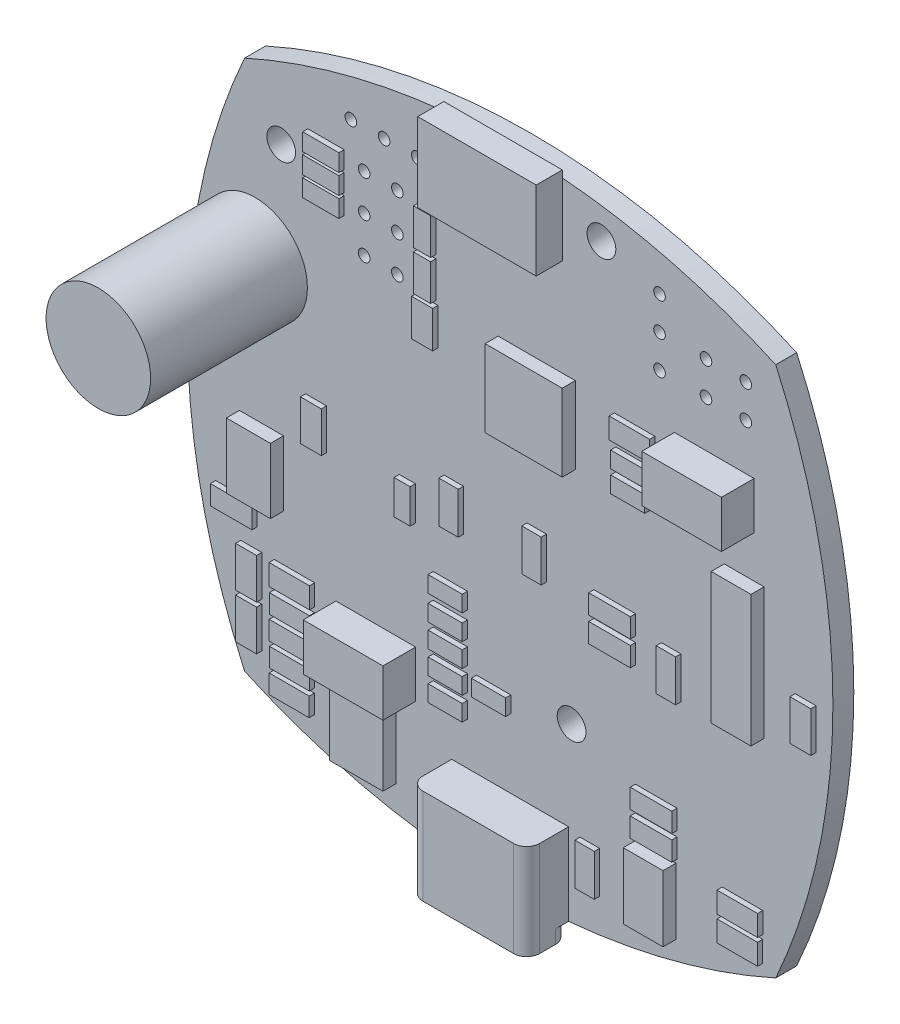
SolidWorks part; units mm, degrees
ref_plane "前视基准面" through (0, 0, 0) normal (0, 0, 1) x (1, 0, 0)
ref_plane "上视基准面" through (0, 0, 0) normal (0, 1, 0) x (1, 0, 0)
ref_plane "右视基准面" through (0, 0, 0) normal (1, 0, 0) x (0, 0, -1)
sketch "Model" plane through (0, 0, 0) normal (0, 0, 1) x (1, 0, 0)
  line L0 (-8.89, -4.699) -> (-11.4046, -4.699)
  line L1 (-11.4046, -4.699) -> (-11.4046, 0.381)
  line L2 (-11.4046, 0.381) -> (-8.89, 0.381)
  line L3 (-8.89, 0.381) -> (-8.89, -4.699)
  line L4 (10.788, 6.8768) -> (10.788, 6.0767)
  line L5 (9.6783, 7.1866) -> (10.4782, 7.1866)
  line L6 (9.6783, 5.767) -> (10.4782, 5.767)
  line L7 (9.1024, 7.1924) -> (8.3024, 7.1924)
  line L8 (7.9925, 6.8826) -> (7.9925, 6.0826)
  line L9 (9.1024, 5.7728) -> (8.3024, 5.7728)
  line L10 (1.432, 0.38) -> (2.632, 0.38)
  line L11 (1.232, -1.67) -> (1.232, -2.67)
  line L12 (2.832, -1.67) -> (2.832, -2.67)
  line L13 (1.232, -0.8699) -> (1.232, 0.13)
  line L14 (2.832, -0.8699) -> (2.832, 0.13)
  line L15 (1.432, -2.92) -> (2.632, -2.92)
  line L16 (1.232, -2.72) -> (1.232, -2.67)
  line L17 (2.832, -2.72) -> (2.832, -2.67)
  line L18 (1.232, 0.18) -> (1.232, 0.13)
  line L19 (2.832, 0.18) -> (2.832, 0.13)
  line L20 (10.788, 8.5278) -> (10.788, 7.7277)
  line L21 (9.6783, 8.8376) -> (10.4782, 8.8376)
  line L22 (9.6783, 7.418) -> (10.4782, 7.418)
  line L23 (9.1024, 8.8434) -> (8.3024, 8.8434)
  line L24 (7.9925, 8.5336) -> (7.9925, 7.7336)
  line L25 (9.1024, 7.4238) -> (8.3024, 7.4238)
  line L26 (-6.7498, 11.296) -> (-5.9497, 11.296)
  line L27 (-7.0596, 10.1863) -> (-7.0596, 10.9862)
  line L28 (-5.64, 10.1863) -> (-5.64, 10.9862)
  line L29 (-7.0654, 9.6104) -> (-7.0654, 8.8104)
  line L30 (-6.7556, 8.5005) -> (-5.9556, 8.5005)
  line L31 (-5.6458, 9.6104) -> (-5.6458, 8.8104)
  line L32 (5.496, -18.416) -> (6.696, -18.416)
  line L33 (5.296, -20.466) -> (5.296, -21.466)
  line L34 (6.896, -20.466) -> (6.896, -21.466)
  line L35 (5.296, -19.6659) -> (5.296, -18.666)
  line L36 (6.896, -19.6659) -> (6.896, -18.666)
  line L37 (5.496, -21.716) -> (6.696, -21.716)
  line L38 (5.296, -21.516) -> (5.296, -21.466)
  line L39 (6.896, -21.516) -> (6.896, -21.466)
  line L40 (5.296, -18.616) -> (5.296, -18.666)
  line L41 (6.896, -18.616) -> (6.896, -18.666)
  line L42 (9.651, -3.591) -> (9.651, -4.791)
  line L43 (7.601, -3.391) -> (6.601, -3.391)
  line L44 (7.601, -4.991) -> (6.601, -4.991)
  line L45 (8.4011, -3.391) -> (9.401, -3.391)
  line L46 (8.4011, -4.991) -> (9.401, -4.991)
  line L47 (6.351, -3.591) -> (6.351, -4.791)
  line L48 (6.551, -3.391) -> (6.601, -3.391)
  line L49 (6.551, -4.991) -> (6.601, -4.991)
  line L50 (9.451, -3.391) -> (9.401, -3.391)
  line L51 (9.451, -4.991) -> (9.401, -4.991)
  line L52 (9.651, -1.686) -> (9.651, -2.886)
  line L53 (7.601, -1.486) -> (6.601, -1.486)
  line L54 (7.601, -3.086) -> (6.601, -3.086)
  line L55 (8.4011, -1.486) -> (9.401, -1.486)
  line L56 (8.4011, -3.086) -> (9.401, -3.086)
  line L57 (6.351, -1.686) -> (6.351, -2.886)
  line L58 (6.551, -1.486) -> (6.601, -1.486)
  line L59 (6.551, -3.086) -> (6.601, -3.086)
  line L60 (9.451, -1.486) -> (9.401, -1.486)
  line L61 (9.451, -3.086) -> (9.401, -3.086)
  line L62 (9.526, -14.189) -> (9.526, -12.989)
  line L63 (11.576, -14.389) -> (12.576, -14.389)
  line L64 (11.576, -12.789) -> (12.576, -12.789)
  line L65 (10.7759, -14.389) -> (9.776, -14.389)
  line L66 (10.7759, -12.789) -> (9.776, -12.789)
  line L67 (12.826, -14.189) -> (12.826, -12.989)
  line L68 (12.626, -14.389) -> (12.576, -14.389)
  line L69 (12.626, -12.789) -> (12.576, -12.789)
  line L70 (9.726, -14.389) -> (9.776, -14.389)
  line L71 (9.726, -12.789) -> (9.776, -12.789)
  line L72 (-3.718, -2.92) -> (-4.918, -2.92)
  line L73 (-3.518, -0.87) -> (-3.518, 0.13)
  line L74 (-5.118, -0.87) -> (-5.118, 0.13)
  line L75 (-3.518, -1.6701) -> (-3.518, -2.67)
  line L76 (-5.118, -1.6701) -> (-5.118, -2.67)
  line L77 (-3.718, 0.38) -> (-4.918, 0.38)
  line L78 (-3.518, 0.18) -> (-3.518, 0.13)
  line L79 (-5.118, 0.18) -> (-5.118, 0.13)
  line L80 (-3.518, -2.72) -> (-3.518, -2.67)
  line L81 (-5.118, -2.72) -> (-5.118, -2.67)
  line L82 (12.919, -5.714) -> (11.719, -5.714)
  line L83 (13.119, -3.664) -> (13.119, -2.664)
  line L84 (11.519, -3.664) -> (11.519, -2.664)
  line L85 (13.119, -4.4641) -> (13.119, -5.464)
  line L86 (11.519, -4.4641) -> (11.519, -5.464)
  line L87 (12.919, -2.414) -> (11.719, -2.414)
  line L88 (13.119, -2.614) -> (13.119, -2.664)
  line L89 (11.519, -2.614) -> (11.519, -2.664)
  line L90 (13.119, -5.514) -> (13.119, -5.464)
  line L91 (11.519, -5.514) -> (11.519, -5.464)
  line L92 (12.826, -14.894) -> (12.826, -16.094)
  line L93 (10.776, -14.694) -> (9.776, -14.694)
  line L94 (10.776, -16.294) -> (9.776, -16.294)
  line L95 (11.5761, -14.694) -> (12.576, -14.694)
  line L96 (11.5761, -16.294) -> (12.576, -16.294)
  line L97 (9.526, -14.894) -> (9.526, -16.094)
  line L98 (9.726, -14.694) -> (9.776, -14.694)
  line L99 (9.726, -16.294) -> (9.776, -16.294)
  line L100 (12.626, -14.694) -> (12.576, -14.694)
  line L101 (12.626, -16.294) -> (12.576, -16.294)
  line L102 (-22.3748, 8.2296) -> (-22.3748, 9.5758)
  line L103 (-21.7398, 8.9154) -> (-22.9844, 8.9154)
  line L104 (-12.354, -2.793) -> (-13.554, -2.793)
  line L105 (-12.154, -0.743) -> (-12.154, 0.257)
  line L106 (-13.754, -0.743) -> (-13.754, 0.257)
  line L107 (-12.154, -1.5431) -> (-12.154, -2.543)
  line L108 (-13.754, -1.5431) -> (-13.754, -2.543)
  line L109 (-12.354, 0.507) -> (-13.554, 0.507)
  line L110 (-12.154, 0.307) -> (-12.154, 0.257)
  line L111 (-13.754, 0.307) -> (-13.754, 0.257)
  line L112 (-12.154, -2.593) -> (-12.154, -2.543)
  line L113 (-13.754, -2.593) -> (-13.754, -2.543)
  line L114 (-22.605, -10.125) -> (-22.605, -8.925)
  line L115 (-20.555, -10.325) -> (-19.555, -10.325)
  line L116 (-20.555, -8.725) -> (-19.555, -8.725)
  line L117 (-21.3551, -10.325) -> (-22.355, -10.325)
  line L118 (-21.3551, -8.725) -> (-22.355, -8.725)
  line L119 (-19.305, -10.125) -> (-19.305, -8.925)
  line L120 (-19.505, -10.325) -> (-19.555, -10.325)
  line L121 (-19.505, -8.725) -> (-19.555, -8.725)
  line L122 (-22.405, -10.325) -> (-22.355, -10.325)
  line L123 (-22.405, -8.725) -> (-22.355, -8.725)
  line L124 (-3.182, -6.7122) -> (-3.182, -7.5123)
  line L125 (-4.2917, -6.4024) -> (-3.4918, -6.4024)
  line L126 (-4.2917, -7.822) -> (-3.4918, -7.822)
  line L127 (-4.8676, -6.3966) -> (-5.6676, -6.3966)
  line L128 (-5.9775, -6.7064) -> (-5.9775, -7.5064)
  line L129 (-4.8676, -7.8162) -> (-5.6676, -7.8162)
  line L130 (-3.182, -8.6172) -> (-3.182, -9.4173)
  line L131 (-4.2917, -8.3074) -> (-3.4918, -8.3074)
  line L132 (-4.2917, -9.727) -> (-3.4918, -9.727)
  line L133 (-4.8676, -8.3016) -> (-5.6676, -8.3016)
  line L134 (-5.9775, -8.6114) -> (-5.9775, -9.4114)
  line L135 (-4.8676, -9.7212) -> (-5.6676, -9.7212)
  line L136 (-3.182, -10.3952) -> (-3.182, -11.1953)
  line L137 (-4.2917, -10.0854) -> (-3.4918, -10.0854)
  line L138 (-4.2917, -11.505) -> (-3.4918, -11.505)
  line L139 (-4.8676, -10.0796) -> (-5.6676, -10.0796)
  line L140 (-5.9775, -10.3894) -> (-5.9775, -11.1894)
  line L141 (-4.8676, -11.4992) -> (-5.6676, -11.4992)
  line L142 (-3.182, -12.1732) -> (-3.182, -12.9733)
  line L143 (-4.2917, -11.8634) -> (-3.4918, -11.8634)
  line L144 (-4.2917, -13.283) -> (-3.4918, -13.283)
  line L145 (-4.8676, -11.8576) -> (-5.6676, -11.8576)
  line L146 (-5.9775, -12.1674) -> (-5.9775, -12.9674)
  line L147 (-4.8676, -13.2772) -> (-5.6676, -13.2772)
  line L148 (-6.3688, -20.835) -> (-5.5687, -20.835)
  line L149 (-6.6786, -21.9447) -> (-6.6786, -21.1448)
  line L150 (-5.259, -21.9447) -> (-5.259, -21.1448)
  line L151 (-6.6844, -22.5206) -> (-6.6844, -23.3206)
  line L152 (-6.3746, -23.6305) -> (-5.5746, -23.6305)
  line L153 (-5.2648, -22.5206) -> (-5.2648, -23.3206)
  line L154 (-7.4742, -4.057) -> (-8.2743, -4.057)
  line L155 (-7.1644, -2.9473) -> (-7.1644, -3.7472)
  line L156 (-8.584, -2.9473) -> (-8.584, -3.7472)
  line L157 (-7.1586, -2.3714) -> (-7.1586, -1.5714)
  line L158 (-7.4684, -1.2615) -> (-8.2684, -1.2615)
  line L159 (-8.5782, -2.3714) -> (-8.5782, -1.5714)
  line L160 (-3.182, -13.9512) -> (-3.182, -14.7513)
  line L161 (-4.2917, -13.6414) -> (-3.4918, -13.6414)
  line L162 (-4.2917, -15.061) -> (-3.4918, -15.061)
  line L163 (-4.8676, -13.6356) -> (-5.6676, -13.6356)
  line L164 (-5.9775, -13.9454) -> (-5.9775, -14.7454)
  line L165 (-4.8676, -15.0552) -> (-5.6676, -15.0552)
  line L166 (-2.66, -12.7188) -> (-2.66, -11.9187)
  line L167 (-1.5503, -13.0286) -> (-2.3502, -13.0286)
  line L168 (-1.5503, -11.609) -> (-2.3502, -11.609)
  line L169 (-0.9744, -13.0344) -> (-0.1744, -13.0344)
  line L170 (0.1355, -12.7246) -> (0.1355, -11.9246)
  line L171 (-0.9744, -11.6148) -> (-0.1744, -11.6148)
  line L172 (-22.86, 0.635) -> (-22.4536, -0.381)
  line L173 (-22.4536, -0.381) -> (-23.2664, -0.381)
  line L174 (-23.2664, -0.381) -> (-22.86, 0.635)
  line L175 (-21.86, 1.627) -> (-21.86, -1.373)
  line L176 (-23.86, 1.627) -> (-23.86, -1.373)
  line L177 (-22.352, 0.635) -> (-23.368, 0.635)
  line L178 (-22.86, 0.889) -> (-22.86, -0.635)
  line L179 (-7.366, 13.081) -> (-7.366, 10.5664)
  line L180 (-7.366, 10.5664) -> (-12.446, 10.5664)
  line L181 (-12.446, 10.5664) -> (-12.446, 13.081)
  line L182 (-12.446, 13.081) -> (-7.366, 13.081)
  line L183 (-7.366, 15.875) -> (-7.366, 13.3604)
  line L184 (-7.366, 13.3604) -> (-12.446, 13.3604)
  line L185 (-12.446, 13.3604) -> (-12.446, 15.875)
  line L186 (-12.446, 15.875) -> (-7.366, 15.875)
  line L187 (-7.366, 18.669) -> (-7.366, 16.1544)
  line L188 (-7.366, 16.1544) -> (-12.446, 16.1544)
  line L189 (-12.446, 16.1544) -> (-12.446, 18.669)
  line L190 (-12.446, 18.669) -> (-7.366, 18.669)
  line L191 (16.764, 19.304) -> (19.2786, 19.304)
  line L192 (19.2786, 19.304) -> (19.2786, 14.224)
  line L193 (19.2786, 14.224) -> (16.764, 14.224)
  line L194 (16.764, 14.224) -> (16.764, 19.304)
  line L195 (13.716, 19.304) -> (16.2306, 19.304)
  line L196 (16.2306, 19.304) -> (16.2306, 14.224)
  line L197 (16.2306, 14.224) -> (13.716, 14.224)
  line L198 (13.716, 14.224) -> (13.716, 19.304)
  line L199 (12.7, 19.939) -> (12.7, 21.844)
  line L200 (12.7, 21.844) -> (10.16, 21.844)
  line L201 (10.16, 21.844) -> (10.16, 14.224)
  line L202 (10.16, 14.224) -> (12.7, 14.224)
  line L203 (12.7, 14.224) -> (12.7, 19.939)
  line L204 (10.922, 4.445) -> (10.922, 1.905)
  line L205 (10.922, 1.905) -> (13.462, 1.905)
  line L206 (13.462, 4.445) -> (13.462, 0.619)
  line L207 (5.842, 0.635) -> (5.842, 3.175)
  line L208 (7.112, 4.445) -> (13.462, 4.445)
  line L209 (12.1873, -0.635) -> (7.112, -0.635)
  line L210 (-14.4212, -6.4426) -> (-14.4212, -4.9288)
  line L211 (-14.4212, -4.9288) -> (-7.1688, -4.9288)
  line L212 (-7.1688, -4.9288) -> (-7.1688, -6.4426)
  line L213 (-14.4212, -10.0674) -> (-14.4212, -11.5812)
  line L214 (-14.4212, -11.5812) -> (-7.1688, -11.5812)
  line L215 (-7.1688, -11.5812) -> (-7.1688, -10.0674)
  line L216 (-16.88, -15.208) -> (-18.03, -15.208)
  line L217 (-18.03, -15.208) -> (-18.03, -13.758)
  line L218 (-18.03, -13.758) -> (-16.83, -13.758)
  line L219 (-16.21, -13.748) -> (-14.97, -13.748)
  line L220 (-14.97, -13.748) -> (-14.97, -15.198)
  line L221 (-14.97, -15.198) -> (-16.21, -15.198)
  line L222 (-18.03, -15.208) -> (-18.06, -15.208)
  line L223 (-18.06, -15.208) -> (-18.26, -15.008)
  line L224 (-18.26, -15.008) -> (-18.26, -13.988)
  line L225 (-18.26, -13.988) -> (-18.23, -13.958)
  line L226 (-18.23, -13.958) -> (-18.03, -13.758)
  line L227 (-16.14, -15.526) -> (-14.99, -15.526)
  line L228 (-14.99, -15.526) -> (-14.99, -16.976)
  line L229 (-14.99, -16.976) -> (-16.19, -16.976)
  line L230 (-16.81, -16.986) -> (-18.05, -16.986)
  line L231 (-18.05, -16.986) -> (-18.05, -15.536)
  line L232 (-18.05, -15.536) -> (-16.81, -15.536)
  line L233 (-14.99, -15.526) -> (-14.96, -15.526)
  line L234 (-14.96, -15.526) -> (-14.76, -15.726)
  line L235 (-14.76, -15.726) -> (-14.76, -16.746)
  line L236 (-14.76, -16.746) -> (-14.79, -16.776)
  line L237 (-14.79, -16.776) -> (-14.99, -16.976)
  line L238 (-16.88, -18.764) -> (-18.03, -18.764)
  line L239 (-18.03, -18.764) -> (-18.03, -17.314)
  line L240 (-18.03, -17.314) -> (-16.83, -17.314)
  line L241 (-16.21, -17.304) -> (-14.97, -17.304)
  line L242 (-14.97, -17.304) -> (-14.97, -18.754)
  line L243 (-14.97, -18.754) -> (-16.21, -18.754)
  line L244 (-18.03, -18.764) -> (-18.06, -18.764)
  line L245 (-18.06, -18.764) -> (-18.26, -18.564)
  line L246 (-18.26, -18.564) -> (-18.26, -17.544)
  line L247 (-18.26, -17.544) -> (-18.23, -17.514)
  line L248 (-18.23, -17.514) -> (-18.03, -17.314)
  line L249 (-16.14, -19.082) -> (-14.99, -19.082)
  line L250 (-14.99, -19.082) -> (-14.99, -20.532)
  line L251 (-14.99, -20.532) -> (-16.19, -20.532)
  line L252 (-16.81, -20.542) -> (-18.05, -20.542)
  line L253 (-18.05, -20.542) -> (-18.05, -19.092)
  line L254 (-18.05, -19.092) -> (-16.81, -19.092)
  line L255 (-14.99, -19.082) -> (-14.96, -19.082)
  line L256 (-14.96, -19.082) -> (-14.76, -19.282)
  line L257 (-14.76, -19.282) -> (-14.76, -20.302)
  line L258 (-14.76, -20.302) -> (-14.79, -20.332)
  line L259 (-14.79, -20.332) -> (-14.99, -20.532)
  line L260 (-13.8788, 5.5902) -> (-15.3312, 5.5902)
  line L261 (-15.3312, 5.5902) -> (-15.3312, 4.5586)
  line L262 (-13.8788, 2.5378) -> (-15.3312, 2.5378)
  line L263 (-15.3312, 2.5378) -> (-15.3312, 3.5694)
  line L264 (-13.8788, 4.5194) -> (-13.8788, 3.6086)
  line L265 (-10.3228, 5.5902) -> (-11.7752, 5.5902)
  line L266 (-11.7752, 5.5902) -> (-11.7752, 4.5586)
  line L267 (-10.3228, 2.5378) -> (-11.7752, 2.5378)
  line L268 (-11.7752, 2.5378) -> (-11.7752, 3.5694)
  line L269 (-10.3228, 4.5194) -> (-10.3228, 3.6086)
  line L270 (-10.3228, 9.1462) -> (-11.7752, 9.1462)
  line L271 (-11.7752, 9.1462) -> (-11.7752, 8.1146)
  line L272 (-10.3228, 6.0938) -> (-11.7752, 6.0938)
  line L273 (-11.7752, 6.0938) -> (-11.7752, 7.1254)
  line L274 (-10.3228, 8.0754) -> (-10.3228, 7.1646)
  line L275 (11.075, 9.36) -> (11.075, 10.96)
  line L276 (9.2243, 10.9549) -> (7.9744, 10.9549)
  line L277 (9.2243, 9.3549) -> (7.9744, 9.3549)
  line L278 (9.8249, 10.96) -> (11.075, 10.96)
  line L279 (9.8249, 9.36) -> (11.075, 9.36)
  line L280 (7.9744, 9.3549) -> (7.9744, 10.9549)
  line L281 (6.124, -7.7051) -> (6.124, -8.0429)
  line L282 (7.9741, -6.374) -> (7.0554, -6.374)
  line L283 (9.7742, -8.9052) -> (9.7742, -9.3741)
  line L284 (9.7742, -6.3741) -> (9.7742, -6.8428)
  line L285 (9.7742, -8.9052) -> (9.7742, -9.3741)
  line L286 (9.7742, -6.3741) -> (9.7742, -6.8428)
  line L287 (9.7742, -9.3741) -> (7.0554, -9.3741)
  line L288 (9.7742, -8.9052) -> (9.7742, -9.3741)
  line L289 (9.7742, -6.3741) -> (9.7742, -6.8428)
  line L290 (7.9741, -6.3741) -> (9.7742, -6.3741)
  line L291 (7.9741, -9.3741) -> (9.7742, -9.3741)
  line L292 (23.406, -0.736) -> (21.806, -0.736)
  line L293 (21.8111, -2.5867) -> (21.8111, -3.8366)
  line L294 (23.4111, -2.5867) -> (23.4111, -3.8366)
  line L295 (21.806, -1.9861) -> (21.806, -0.736)
  line L296 (23.406, -1.9861) -> (23.406, -0.736)
  line L297 (23.4111, -3.8366) -> (21.8111, -3.8366)
  line L298 (12.093, -7.7051) -> (12.093, -8.0429)
  line L299 (13.9431, -6.374) -> (13.0244, -6.374)
  line L300 (15.7432, -8.9052) -> (15.7432, -9.3741)
  line L301 (15.7432, -6.3741) -> (15.7432, -6.8428)
  line L302 (15.7432, -8.9052) -> (15.7432, -9.3741)
  line L303 (15.7432, -6.3741) -> (15.7432, -6.8428)
  line L304 (15.7432, -9.3741) -> (13.0244, -9.3741)
  line L305 (15.7432, -8.9052) -> (15.7432, -9.3741)
  line L306 (15.7432, -6.3741) -> (15.7432, -6.8428)
  line L307 (13.9431, -6.3741) -> (15.7432, -6.3741)
  line L308 (13.9431, -9.3741) -> (15.7432, -9.3741)
  line L309 (16.23, -16.345) -> (16.23, -17.945)
  line L310 (18.0807, -17.9399) -> (19.3306, -17.9399)
  line L311 (18.0807, -16.3399) -> (19.3306, -16.3399)
  line L312 (17.4801, -17.945) -> (16.23, -17.945)
  line L313 (17.4801, -16.345) -> (16.23, -16.345)
  line L314 (19.3306, -16.3399) -> (19.3306, -17.9399)
  line L315 (19.33, -19.85) -> (19.33, -18.25)
  line L316 (17.4793, -18.2551) -> (16.2294, -18.2551)
  line L317 (17.4793, -19.8551) -> (16.2294, -19.8551)
  line L318 (18.0799, -18.25) -> (19.33, -18.25)
  line L319 (18.0799, -19.85) -> (19.33, -19.85)
  line L320 (16.2294, -19.8551) -> (16.2294, -18.2551)
  line L321 (-18.06, -11.773) -> (-18.06, -13.373)
  line L322 (-16.2093, -13.3679) -> (-14.9594, -13.3679)
  line L323 (-16.2093, -11.7679) -> (-14.9594, -11.7679)
  line L324 (-16.8099, -13.373) -> (-18.06, -13.373)
  line L325 (-16.8099, -11.773) -> (-18.06, -11.773)
  line L326 (-14.9594, -11.7679) -> (-14.9594, -13.3679)
  line L327 (-20.612, -18.314) -> (-19.012, -18.314)
  line L328 (-19.0171, -16.4633) -> (-19.0171, -15.2134)
  line L329 (-20.6171, -16.4633) -> (-20.6171, -15.2134)
  line L330 (-19.012, -17.0639) -> (-19.012, -18.314)
  line L331 (-20.612, -17.0639) -> (-20.612, -18.314)
  line L332 (-20.6171, -15.2134) -> (-19.0171, -15.2134)
  line L333 (-20.612, -14.885) -> (-19.012, -14.885)
  line L334 (-19.0171, -13.0343) -> (-19.0171, -11.7844)
  line L335 (-20.6171, -13.0343) -> (-20.6171, -11.7844)
  line L336 (-19.012, -13.6349) -> (-19.012, -14.885)
  line L337 (-20.612, -13.6349) -> (-20.612, -14.885)
  line L338 (-20.6171, -11.7844) -> (-19.0171, -11.7844)
  line L339 (-14.059, 0.407) -> (-15.659, 0.407)
  line L340 (-15.6539, -1.4437) -> (-15.6539, -2.6936)
  line L341 (-14.0539, -1.4437) -> (-14.0539, -2.6936)
  line L342 (-15.659, -0.8431) -> (-15.659, 0.407)
  line L343 (-14.059, -0.8431) -> (-14.059, 0.407)
  line L344 (-14.0539, -2.6936) -> (-15.6539, -2.6936)
  line L345 (-5.3084, -18.4968) -> (-5.3084, -17.5379)
  line L346 (-5.3084, -17.5379) -> (-6.6296, -17.5379)
  line L347 (-6.6296, -17.5379) -> (-6.6296, -18.4968)
  line L348 (-5.3084, -19.3492) -> (-5.3084, -20.3081)
  line L349 (-5.3084, -20.3081) -> (-6.6296, -20.3081)
  line L350 (-6.6296, -20.3081) -> (-6.6296, -19.3492)
  line L351 (0.28, -15.151) -> (0.28, -13.551)
  line L352 (-1.5707, -13.5561) -> (-2.8206, -13.5561)
  line L353 (-1.5707, -15.1561) -> (-2.8206, -15.1561)
  line L354 (-0.9701, -13.551) -> (0.28, -13.551)
  line L355 (-0.9701, -15.151) -> (0.28, -15.151)
  line L356 (-2.8206, -15.1561) -> (-2.8206, -13.5561)
  line L357 (-13.6708, 13.6904) -> (-12.7119, 13.6904)
  line L358 (-12.7119, 13.6904) -> (-12.7119, 15.0116)
  line L359 (-12.7119, 15.0116) -> (-13.6708, 15.0116)
  line L360 (-14.5232, 13.6904) -> (-15.4821, 13.6904)
  line L361 (-15.4821, 13.6904) -> (-15.4821, 15.0116)
  line L362 (-15.4821, 15.0116) -> (-14.5232, 15.0116)
  line L363 (-14.5232, 16.5356) -> (-15.4821, 16.5356)
  line L364 (-15.4821, 16.5356) -> (-15.4821, 15.2144)
  line L365 (-15.4821, 15.2144) -> (-14.5232, 15.2144)
  line L366 (-13.6708, 16.5356) -> (-12.7119, 16.5356)
  line L367 (-12.7119, 16.5356) -> (-12.7119, 15.2144)
  line L368 (-12.7119, 15.2144) -> (-13.6708, 15.2144)
  line L369 (-14.5232, 18.0596) -> (-15.4821, 18.0596)
  line L370 (-15.4821, 18.0596) -> (-15.4821, 16.7384)
  line L371 (-15.4821, 16.7384) -> (-14.5232, 16.7384)
  line L372 (-13.6708, 18.0596) -> (-12.7119, 18.0596)
  line L373 (-12.7119, 18.0596) -> (-12.7119, 16.7384)
  line L374 (-12.7119, 16.7384) -> (-13.6708, 16.7384)
  line L375 (-5.6894, 13.3802) -> (-5.6894, 14.3391)
  line L376 (-5.6894, 14.3391) -> (-7.0106, 14.3391)
  line L377 (-7.0106, 14.3391) -> (-7.0106, 13.3802)
  line L378 (-5.6894, 12.5278) -> (-5.6894, 11.5689)
  line L379 (-5.6894, 11.5689) -> (-7.0106, 11.5689)
  line L380 (-7.0106, 11.5689) -> (-7.0106, 12.5278)
  line L381 (-5.6894, 16.4282) -> (-5.6894, 17.3871)
  line L382 (-5.6894, 17.3871) -> (-7.0106, 17.3871)
  line L383 (-7.0106, 17.3871) -> (-7.0106, 16.4282)
  line L384 (-5.6894, 15.5758) -> (-5.6894, 14.6169)
  line L385 (-5.6894, 14.6169) -> (-7.0106, 14.6169)
  line L386 (-7.0106, 14.6169) -> (-7.0106, 15.5758)
  line L387 (12.571, 11.96) -> (18.671, 11.96)
  line L388 (12.571, 8.36) -> (18.671, 8.36)
  line L389 (13.081, 11.43) -> (18.161, 11.43)
  line L390 (18.161, 11.43) -> (18.161, 10.8911)
  line L391 (12.571, 11.96) -> (12.571, 10.8911)
  line L392 (12.571, 9.4289) -> (12.571, 8.36)
  line L393 (18.671, 11.96) -> (18.671, 10.8911)
  line L394 (18.671, 9.4289) -> (18.671, 8.36)
  line L395 (18.161, 9.4289) -> (18.161, 8.89)
  line L396 (18.161, 8.89) -> (13.081, 8.89)
  line L397 (13.081, 8.89) -> (13.081, 9.4289)
  line L398 (13.081, 10.8911) -> (13.081, 11.43)
  line L399 (14.351, 10.795) -> (17.018, 10.795)
  line L400 (17.018, 10.795) -> (17.018, 9.525)
  line L401 (17.018, 9.525) -> (14.351, 9.525)
  line L402 (14.351, 9.525) -> (14.351, 10.795)
  line L403 (-7.237, -15.77) -> (-13.337, -15.77)
  line L404 (-7.237, -12.17) -> (-13.337, -12.17)
  line L405 (-7.747, -15.24) -> (-12.827, -15.24)
  line L406 (-12.827, -15.24) -> (-12.827, -14.7011)
  line L407 (-7.237, -15.77) -> (-7.237, -14.7011)
  line L408 (-7.237, -13.2389) -> (-7.237, -12.17)
  line L409 (-13.337, -15.77) -> (-13.337, -14.7011)
  line L410 (-13.337, -13.2389) -> (-13.337, -12.17)
  line L411 (-12.827, -13.2389) -> (-12.827, -12.7)
  line L412 (-12.827, -12.7) -> (-7.747, -12.7)
  line L413 (-7.747, -12.7) -> (-7.747, -13.2389)
  line L414 (-7.747, -14.7011) -> (-7.747, -15.24)
  line L415 (-9.017, -14.605) -> (-11.684, -14.605)
  line L416 (-11.684, -14.605) -> (-11.684, -13.335)
  line L417 (-11.684, -13.335) -> (-9.017, -13.335)
  line L418 (-9.017, -13.335) -> (-9.017, -14.605)
  line L419 (4.982, 11.5987) -> (-0.918, 11.5987)
  line L420 (-0.918, 11.5987) -> (-0.918, 5.6987)
  line L421 (-0.918, 5.6987) -> (4.982, 5.6987)
  line L422 (4.982, 5.6987) -> (4.982, 11.5987)
  line L423 (16.3856, 5.1532) -> (19.4284, 5.1532)
  line L424 (19.4284, 5.1532) -> (19.4284, -4.8992)
  line L425 (19.4284, -4.8992) -> (16.3856, -4.8992)
  line L426 (16.3856, -4.8992) -> (16.3856, 5.1532)
  line L427 (-18.45, -3.225) -> (-17.35, -3.225)
  line L428 (-17.35, -3.225) -> (-17.35, -8.215)
  line L429 (-17.35, -8.215) -> (-20.7212, -8.215)
  line L430 (-20.7212, -8.215) -> (-20.7212, -3.225)
  line L431 (-20.7212, -3.225) -> (-19.63, -3.225)
  line L432 (9.6546, -16.5238) -> (12.6974, -16.5238)
  line L433 (12.6974, -16.5238) -> (12.6974, -21.5762)
  line L434 (12.6974, -21.5762) -> (9.6546, -21.5762)
  line L435 (9.6546, -21.5762) -> (9.6546, -16.5238)
  line L436 (-8.745, -16.8811) -> (-8.745, -21.9812)
  line L437 (-8.745, -21.9809) -> (-12.845, -21.9809)
  line L438 (-12.845, -21.9809) -> (-12.845, -16.8808)
  line L439 (-9.9949, -16.8811) -> (-8.745, -16.8811)
  line L440 (-11.5951, -16.8811) -> (-12.845, -16.8811)
  line L441 (4.32, -25.527) -> (-4.32, -25.527)
  line L442 (-4.32, -20.0028) -> (-4.32, -21.9212)
  line L443 (4.32, -20.0028) -> (4.32, -21.9212)
  line L444 (0.9571, 0.4299) -> (-3.2429, 0.4299)
  line L445 (-3.2429, 0.4299) -> (-3.2429, -2.9701)
  line L446 (-3.2429, -2.9701) -> (0.9571, -2.9701)
  line L447 (0.9571, -2.9701) -> (0.9571, 0.4299)
  line L448 (-16.8, 2.127) -> (-16.8, -1.873)
  line L449 (-21.3, -1.873) -> (-21.3, 2.127)
  line L450 (-4.9489, 20.193) -> (-4.9489, 18.943)
  line L451 (-4.9489, 18.943) -> (-2.9489, 18.943)
  line L452 (-5.0759, 25.07) -> (3.9921, 25.07)
  line L453 (3.9913, 20.2832) -> (3.9913, 19.0335)
  line L454 (3.9913, 19.0335) -> (1.9923, 19.0335)
  line L455 (-5.0759, 23.114) -> (-5.0759, 25.0759)
  line L456 (3.9921, 25.02) -> (3.9921, 23.033)
  line L457 (-11.557, 21.59) -> (-13.462, 21.59)
  line L458 (-13.462, 21.59) -> (-13.462, 19.05)
  line L459 (-13.462, 19.05) -> (-5.842, 19.05)
  line L460 (-5.842, 19.05) -> (-5.842, 21.59)
  line L461 (-5.842, 21.59) -> (-11.557, 21.59)
  line L462 (-4.62, -22.627) -> (-4.62, -23.227)
  line L463 (-4.62, -23.227) -> (-4.62, -22.627)
  line L464 (-4.02, -22.627) -> (-4.02, -23.227)
  line L465 (-4.02, -23.227) -> (-4.02, -22.627)
  line L466 (4.02, -22.627) -> (4.02, -23.227)
  line L467 (4.02, -23.227) -> (4.02, -22.627)
  line L468 (4.62, -22.627) -> (4.62, -23.227)
  line L469 (4.62, -23.227) -> (4.62, -22.627)
  line L470 (4.02, -18.1971) -> (4.02, -19.2971)
  line L471 (4.02, -19.2971) -> (4.02, -18.1971)
  line L472 (4.62, -18.1971) -> (4.62, -19.2971)
  line L473 (4.62, -19.2971) -> (4.62, -18.1971)
  line L474 (-4.62, -18.1971) -> (-4.62, -19.2971)
  line L475 (-4.62, -19.2971) -> (-4.62, -18.1971)
  line L476 (-4.02, -18.1971) -> (-4.02, -19.2971)
  line L477 (-4.02, -19.2971) -> (-4.02, -18.1971)
  line L478 (9.652, 14.605) -> (9.652, 21.1137) construction
  line L479 (22.987, -0.127) -> (22.987, 2.8893) construction
  line L480 (-3.937, 9.017) -> (-3.937, 16.7322) construction
  arc A0 (-20, -20) -> (20, -20) centre (0, 20.32) ccw
  arc A1 (-20, 20) -> (-20, -20) centre (20.32, 0) ccw
  arc A2 (20, -20) -> (19.9956, 19.9978) centre (-20, -0.0056) ccw
  arc A3 (20, 20) -> (-19.9992, 19.9983) centre (0.0021, -20) ccw
  arc A4 (8.3023, 7.1924) -> (7.9925, 6.8826) centre (8.3023, 6.8826) ccw
  arc A5 (7.9925, 6.0826) -> (8.3023, 5.7728) centre (8.3023, 6.0826) ccw
  arc A6 (10.788, 6.8768) -> (10.4782, 7.1866) centre (10.4782, 6.8768) ccw
  arc A7 (10.4782, 5.767) -> (10.788, 6.0768) centre (10.4782, 6.0768) ccw
  arc A8 (1.232, -2.72) -> (1.432, -2.92) centre (1.432, -2.72) ccw
  arc A9 (2.632, -2.92) -> (2.832, -2.72) centre (2.632, -2.72) ccw
  arc A10 (1.432, 0.38) -> (1.232, 0.18) centre (1.432, 0.18) ccw
  arc A11 (2.832, 0.18) -> (2.632, 0.38) centre (2.632, 0.18) ccw
  arc A12 (8.3023, 8.8434) -> (7.9925, 8.5336) centre (8.3023, 8.5336) ccw
  arc A13 (7.9925, 7.7336) -> (8.3023, 7.4238) centre (8.3023, 7.7336) ccw
  arc A14 (10.788, 8.5278) -> (10.4782, 8.8376) centre (10.4782, 8.5278) ccw
  arc A15 (10.4782, 7.418) -> (10.788, 7.7278) centre (10.4782, 7.7278) ccw
  arc A16 (-7.0654, 8.8103) -> (-6.7556, 8.5005) centre (-6.7556, 8.8103) ccw
  arc A17 (-5.9556, 8.5005) -> (-5.6458, 8.8103) centre (-5.9556, 8.8103) ccw
  arc A18 (-6.7498, 11.296) -> (-7.0596, 10.9862) centre (-6.7498, 10.9862) ccw
  arc A19 (-5.64, 10.9862) -> (-5.9498, 11.296) centre (-5.9498, 10.9862) ccw
  arc A20 (5.296, -21.516) -> (5.496, -21.716) centre (5.496, -21.516) ccw
  arc A21 (6.696, -21.716) -> (6.896, -21.516) centre (6.696, -21.516) ccw
  arc A22 (5.496, -18.416) -> (5.296, -18.616) centre (5.496, -18.616) ccw
  arc A23 (6.896, -18.616) -> (6.696, -18.416) centre (6.696, -18.616) ccw
  arc A24 (6.551, -3.391) -> (6.351, -3.591) centre (6.551, -3.591) ccw
  arc A25 (6.351, -4.791) -> (6.551, -4.991) centre (6.551, -4.791) ccw
  arc A26 (9.651, -3.591) -> (9.451, -3.391) centre (9.451, -3.591) ccw
  arc A27 (9.451, -4.991) -> (9.651, -4.791) centre (9.451, -4.791) ccw
  arc A28 (6.551, -1.486) -> (6.351, -1.686) centre (6.551, -1.686) ccw
  arc A29 (6.351, -2.886) -> (6.551, -3.086) centre (6.551, -2.886) ccw
  arc A30 (9.651, -1.686) -> (9.451, -1.486) centre (9.451, -1.686) ccw
  arc A31 (9.451, -3.086) -> (9.651, -2.886) centre (9.451, -2.886) ccw
  arc A32 (12.626, -14.389) -> (12.826, -14.189) centre (12.626, -14.189) ccw
  arc A33 (12.826, -12.989) -> (12.626, -12.789) centre (12.626, -12.989) ccw
  arc A34 (9.526, -14.189) -> (9.726, -14.389) centre (9.726, -14.189) ccw
  arc A35 (9.726, -12.789) -> (9.526, -12.989) centre (9.726, -12.989) ccw
  arc A36 (-3.518, 0.18) -> (-3.718, 0.38) centre (-3.718, 0.18) ccw
  arc A37 (-4.918, 0.38) -> (-5.118, 0.18) centre (-4.918, 0.18) ccw
  arc A38 (-3.718, -2.92) -> (-3.518, -2.72) centre (-3.718, -2.72) ccw
  arc A39 (-5.118, -2.72) -> (-4.918, -2.92) centre (-4.918, -2.72) ccw
  arc A40 (13.119, -2.614) -> (12.919, -2.414) centre (12.919, -2.614) ccw
  arc A41 (11.719, -2.414) -> (11.519, -2.614) centre (11.719, -2.614) ccw
  arc A42 (12.919, -5.714) -> (13.119, -5.514) centre (12.919, -5.514) ccw
  arc A43 (11.519, -5.514) -> (11.719, -5.714) centre (11.719, -5.514) ccw
  arc A44 (9.726, -14.694) -> (9.526, -14.894) centre (9.726, -14.894) ccw
  arc A45 (9.526, -16.094) -> (9.726, -16.294) centre (9.726, -16.094) ccw
  arc A46 (12.826, -14.894) -> (12.626, -14.694) centre (12.626, -14.894) ccw
  arc A47 (12.626, -16.294) -> (12.826, -16.094) centre (12.626, -16.094) ccw
  arc A48 (-19.5199, 11.4937) -> (-19.4843, 11.4935) centre (-19.5199, 7.4937) ccw
  arc A49 (-12.154, 0.307) -> (-12.354, 0.507) centre (-12.354, 0.307) ccw
  arc A50 (-13.554, 0.507) -> (-13.754, 0.307) centre (-13.554, 0.307) ccw
  arc A51 (-12.354, -2.793) -> (-12.154, -2.593) centre (-12.354, -2.593) ccw
  arc A52 (-13.754, -2.593) -> (-13.554, -2.793) centre (-13.554, -2.593) ccw
  arc A53 (-19.505, -10.325) -> (-19.305, -10.125) centre (-19.505, -10.125) ccw
  arc A54 (-19.305, -8.925) -> (-19.505, -8.725) centre (-19.505, -8.925) ccw
  arc A55 (-22.605, -10.125) -> (-22.405, -10.325) centre (-22.405, -10.125) ccw
  arc A56 (-22.405, -8.725) -> (-22.605, -8.925) centre (-22.405, -8.925) ccw
  arc A57 (-5.6677, -6.3966) -> (-5.9775, -6.7064) centre (-5.6677, -6.7064) ccw
  arc A58 (-5.9775, -7.5064) -> (-5.6677, -7.8162) centre (-5.6677, -7.5064) ccw
  arc A59 (-3.182, -6.7122) -> (-3.4918, -6.4024) centre (-3.4918, -6.7122) ccw
  arc A60 (-3.4918, -7.822) -> (-3.182, -7.5122) centre (-3.4918, -7.5122) ccw
  arc A61 (-5.6677, -8.3016) -> (-5.9775, -8.6114) centre (-5.6677, -8.6114) ccw
  arc A62 (-5.9775, -9.4114) -> (-5.6677, -9.7212) centre (-5.6677, -9.4114) ccw
  arc A63 (-3.182, -8.6172) -> (-3.4918, -8.3074) centre (-3.4918, -8.6172) ccw
  arc A64 (-3.4918, -9.727) -> (-3.182, -9.4172) centre (-3.4918, -9.4172) ccw
  arc A65 (-5.6677, -10.0796) -> (-5.9775, -10.3894) centre (-5.6677, -10.3894) ccw
  arc A66 (-5.9775, -11.1894) -> (-5.6677, -11.4992) centre (-5.6677, -11.1894) ccw
  arc A67 (-3.182, -10.3952) -> (-3.4918, -10.0854) centre (-3.4918, -10.3952) ccw
  arc A68 (-3.4918, -11.505) -> (-3.182, -11.1952) centre (-3.4918, -11.1952) ccw
  arc A69 (-5.6677, -11.8576) -> (-5.9775, -12.1674) centre (-5.6677, -12.1674) ccw
  arc A70 (-5.9775, -12.9674) -> (-5.6677, -13.2772) centre (-5.6677, -12.9674) ccw
  arc A71 (-3.182, -12.1732) -> (-3.4918, -11.8634) centre (-3.4918, -12.1732) ccw
  arc A72 (-3.4918, -13.283) -> (-3.182, -12.9732) centre (-3.4918, -12.9732) ccw
  arc A73 (-6.6844, -23.3207) -> (-6.3746, -23.6305) centre (-6.3746, -23.3207) ccw
  arc A74 (-5.5746, -23.6305) -> (-5.2648, -23.3207) centre (-5.5746, -23.3207) ccw
  arc A75 (-6.3688, -20.835) -> (-6.6786, -21.1448) centre (-6.3688, -21.1448) ccw
  arc A76 (-5.259, -21.1448) -> (-5.5688, -20.835) centre (-5.5688, -21.1448) ccw
  arc A77 (-7.1586, -1.5713) -> (-7.4684, -1.2615) centre (-7.4684, -1.5713) ccw
  arc A78 (-8.2684, -1.2615) -> (-8.5782, -1.5713) centre (-8.2684, -1.5713) ccw
  arc A79 (-7.4742, -4.057) -> (-7.1644, -3.7472) centre (-7.4742, -3.7472) ccw
  arc A80 (-8.584, -3.7472) -> (-8.2742, -4.057) centre (-8.2742, -3.7472) ccw
  arc A81 (-5.6677, -13.6356) -> (-5.9775, -13.9454) centre (-5.6677, -13.9454) ccw
  arc A82 (-5.9775, -14.7454) -> (-5.6677, -15.0552) centre (-5.6677, -14.7454) ccw
  arc A83 (-3.182, -13.9512) -> (-3.4918, -13.6414) centre (-3.4918, -13.9512) ccw
  arc A84 (-3.4918, -15.061) -> (-3.182, -14.7512) centre (-3.4918, -14.7512) ccw
  arc A85 (-0.1743, -13.0344) -> (0.1355, -12.7246) centre (-0.1743, -12.7246) ccw
  arc A86 (0.1355, -11.9246) -> (-0.1743, -11.6148) centre (-0.1743, -11.9246) ccw
  arc A87 (-2.66, -12.7188) -> (-2.3502, -13.0286) centre (-2.3502, -12.7188) ccw
  arc A88 (-2.3502, -11.609) -> (-2.66, -11.9188) centre (-2.3502, -11.9188) ccw
  arc A89 (12.192, -0.635) -> (13.4619, 0.619) centre (12.192, 0.635) ccw
  arc A90 (5.842, 0.635) -> (7.112, -0.635) centre (7.112, 0.635) ccw
  arc A91 (7.112, 4.445) -> (5.842, 3.175) centre (7.112, 3.175) ccw
  arc A92 (-2.032, 12.3952) -> (-2.032, 12.3927) centre (-2.182, 12.3939) ccw
  arc A93 (0.033, 10.8483) -> (0.033, 10.8458) centre (-0.167, 10.8471) ccw
  arc A94 (-2.794, 11.3073) -> (-2.794, 11.6035) centre (-2.794, 11.4554) ccw
  arc A95 (-2.794, 11.6035) -> (-2.794, 11.3073) centre (-2.794, 11.4554) ccw
  arc A96 (-19.63, -3.225) -> (-18.45, -3.225) centre (-19.04, -3.225) ccw
  arc A97 (-11.5951, -16.9311) -> (-9.9949, -16.9311) centre (-10.795, -16.5558) ccw
  arc A98 (0.757, 0.7797) -> (0.7558, 0.7797) centre (0.7558, 0.9297) ccw
  circle A99 centre (-17.526, 16.002) radius 1.5999
  circle A100 centre (4.699, -11.303) radius 1.5999
  circle A101 centre (6.985, 21.844) radius 1.5999
  circle A102 centre (-13.1549, 3.114) radius 0.1001
  circle A103 centre (-9.5989, 3.114) radius 0.1001
  circle A104 centre (-9.5989, 6.67) radius 0.1001
  circle A105 centre (7.8989, -7.8743) radius 0.4752
  circle A106 centre (13.8679, -7.8743) radius 0.4752
  circle A107 centre (-2.794, 11.4554) radius 0.127
  circle A108 centre (17.1379, 4.572) radius 0.1501
  circle A109 centre (15.1714, 5.3254) radius 0.1501
  circle A110 centre (14.507, 4.572) radius 0.2499
  circle A111 centre (10.4069, -17.145) radius 0.1501
  circle A112 centre (8.4082, -16.4056) radius 0.1501
  circle A113 centre (7.7785, -17.145) radius 0.1501
  circle A114 centre (-14.0749, -17.4711) radius 0.1501
  circle A115 centre (-13.2951, -16.401) radius 0.1702
  circle A116 centre (-10.16, -3.429) radius 0.4445
  circle A117 centre (-10.16, -3.429) radius 0.7874
  circle A118 centre (-17.8079, 7.493) radius 0.5
  circle A119 centre (-17.8079, 7.493) radius 0.8
  circle A120 centre (-21.3081, 7.493) radius 0.5
  circle A121 centre (-21.3081, 7.493) radius 0.8
  circle A122 centre (-8.636, 11.811) radius 0.4445
  circle A123 centre (-8.636, 11.811) radius 0.7874
  circle A124 centre (-8.636, 14.605) radius 0.4445
  circle A125 centre (-8.636, 14.605) radius 0.7874
  circle A126 centre (-8.636, 17.399) radius 0.4445
  circle A127 centre (-8.636, 17.399) radius 0.7874
  circle A128 centre (18.034, 18.034) radius 0.4445
  circle A129 centre (18.034, 18.034) radius 0.7874
  circle A130 centre (14.986, 18.034) radius 0.4445
  circle A131 centre (14.986, 18.034) radius 0.7874
  circle A132 centre (11.43, 15.494) radius 0.4445
  circle A133 centre (11.43, 15.494) radius 0.7874
  circle A134 centre (11.43, 18.034) radius 0.4445
  circle A135 centre (11.43, 18.034) radius 0.7874
  circle A136 centre (12.192, 3.175) radius 0.4572
  circle A137 centre (12.192, 3.175) radius 0.762
  circle A138 centre (12.192, 0.635) radius 0.4572
  circle A139 centre (12.192, 0.635) radius 0.762
  circle A140 centre (9.652, 3.175) radius 0.4572
  circle A141 centre (9.652, 3.175) radius 0.762
  circle A142 centre (9.652, 0.635) radius 0.4572
  circle A143 centre (9.652, 0.635) radius 0.762
  circle A144 centre (7.112, 3.175) radius 0.4572
  circle A145 centre (7.112, 3.175) radius 0.762
  circle A146 centre (7.112, 0.635) radius 0.4572
  circle A147 centre (7.112, 0.635) radius 0.762
  circle A148 centre (-7.112, 20.32) radius 0.4445
  circle A149 centre (-7.112, 20.32) radius 0.7874
  circle A150 centre (-9.652, 20.32) radius 0.4445
  circle A151 centre (-9.652, 20.32) radius 0.7874
  circle A152 centre (-10.16, -0.889) radius 0.4445
  circle A153 centre (-11.176, 11.811) radius 0.4445
  circle A154 centre (-11.176, 14.605) radius 0.4445
  circle A155 centre (-11.176, 17.399) radius 0.4445
  circle A156 centre (18.034, 15.494) radius 0.4445
  circle A157 centre (14.986, 15.494) radius 0.4445
  circle A158 centre (11.43, 20.574) radius 0.4445
  arc A159 (-4.62, -22.627) -> (-4.02, -22.627) centre (-4.32, -22.627) ccw
  arc A160 (-4.02, -23.227) -> (-4.62, -23.227) centre (-4.32, -23.227) ccw
  arc A161 (4.02, -22.627) -> (4.62, -22.627) centre (4.32, -22.627) ccw
  arc A162 (4.62, -23.227) -> (4.02, -23.227) centre (4.32, -23.227) ccw
  arc A163 (4.02, -18.1971) -> (4.62, -18.1971) centre (4.32, -18.1971) ccw
  arc A164 (4.62, -19.2971) -> (4.02, -19.2971) centre (4.32, -19.2971) ccw
  arc A165 (-4.62, -18.1971) -> (-4.02, -18.1971) centre (-4.32, -18.1971) ccw
  arc A166 (-4.02, -19.2971) -> (-4.62, -19.2971) centre (-4.32, -19.2971) ccw
  circle A167 centre (-12.192, 20.32) radius 0.4445
  circle A168 centre (-7.8867, -21.336) radius 0.3048
  circle A169 centre (-7.0371, -13.97) radius 0.3048
  circle A170 centre (-13.716, -17.526) radius 0.3048
  circle A171 centre (-5.272, -14.351) radius 0.3048
  circle A172 centre (-13.208, -15.24) radius 0.3048
  circle A173 centre (-10.922, -16.002) radius 0.3048
  circle A174 centre (-5.969, -18.1696) radius 0.3048
  circle A175 centre (8.382, -18.415) radius 0.3048
  circle A176 centre (-0.2299, -16.637) radius 0.3048
  circle A177 centre (-20.193, -4.318) radius 0.3048
  circle A178 centre (-22.86, 0.381) radius 0.3048
  circle A179 centre (-14.859, -0.3432) radius 0.3048
  circle A180 centre (-16.3101, -3.81) radius 0.3048
  circle A181 centre (6.096, -19.1658) radius 0.3048
  circle A182 centre (13.9438, -18.415) radius 0.3048
  circle A183 centre (18.5801, -17.145) radius 0.3048
  circle A184 centre (1.6383, 13.0175) radius 0.3048
  circle A185 centre (4.699, 10.16) radius 0.3048
  circle A186 centre (8.7249, 10.16) radius 0.3048
  circle A187 centre (-0.7722, 4.2545) radius 0.3048
  circle A188 centre (0.0279, 4.2545) radius 0.3048
  circle A189 centre (2.4257, 4.2545) radius 0.3048
  circle A190 centre (0.828, 4.2545) radius 0.3048
  circle A191 centre (11.43, 12.319) radius 0.3048
  circle A192 centre (0.0381, 13.0175) radius 0.3048
  circle A193 centre (0.8382, 13.0175) radius 0.3048
  circle A194 centre (-7.747, 3.683) radius 0.3048
  circle A195 centre (-7.747, 4.572) radius 0.3048
  circle A196 centre (-7.747, 5.461) radius 0.3048
  circle A197 centre (-14.8504, 17.399) radius 0.3048
  circle A198 centre (-14.8504, 15.875) radius 0.3048
  circle A199 centre (-14.8504, 14.351) radius 0.3048
  circle A200 centre (-6.35, 12.2006) radius 0.3048
  circle A201 centre (8.636, -12.827) radius 0.3048
  circle A202 centre (15.494, -15.621) radius 0.3048
  circle A203 centre (10.795, 5.461) radius 0.3048
  circle A204 centre (10.3248, 10.16) radius 0.3048
  circle A205 centre (1.778, -10.541) radius 0.3048
  circle A206 centre (2.667, -10.541) radius 0.3048
  circle A207 centre (1.778, 2.286) radius 0.3048
  circle A208 centre (2.54, 2.286) radius 0.3048
  circle A209 centre (3.302, 7.62) radius 0.3048
  circle A210 centre (4.191, 7.62) radius 0.3048
  circle A211 centre (-6.35, 10.606) radius 0.3048
  circle A212 centre (-10.049, 8.57) radius 0.3048
  circle A213 centre (-10.049, 5.014) radius 0.3048
  circle A214 centre (-2.3368, 9.8527) radius 0.3048
  circle A215 centre (-0.762, 8.509) radius 0.3048
  circle A216 centre (10.098, 8.255) radius 0.3048
  circle A217 centre (10.098, 6.477) radius 0.3048
  circle A218 centre (15.1714, 3.302) radius 0.3048
  circle A219 centre (20.6426, 3.302) radius 0.3048
  circle A220 centre (18.8709, 10.16) radius 0.3048
  circle A221 centre (12.319, -3.1641) radius 0.3048
  circle A222 centre (2.032, -2.1699) radius 0.3048
  circle A223 centre (-0.0429, -2.0701) radius 0.3048
  circle A224 centre (-2.2431, -0.4699) radius 0.3048
  circle A225 centre (-4.318, -0.3701) radius 0.3048
  circle A226 centre (-7.874, -1.967) radius 0.3048
  circle A227 centre (-12.954, -0.2431) radius 0.3048
  circle A228 centre (-3.872, -7.112) radius 0.3048
  circle A229 centre (-3.872, -9.017) radius 0.3048
  circle A230 centre (-3.872, -10.795) radius 0.3048
  circle A231 centre (-3.872, -12.573) radius 0.3048
  circle A232 centre (-3.872, -14.351) radius 0.3048
  circle A233 centre (-1.97, -12.319) radius 0.3048
  circle A234 centre (-10.795, -18.542) radius 0.3048
  circle A235 centre (-11.43, -18.542) radius 0.3048
  circle A236 centre (-11.43, -19.177) radius 0.3048
  circle A237 centre (-10.795, -19.177) radius 0.3048
  circle A238 centre (-11.43, -19.812) radius 0.3048
  circle A239 centre (-10.795, -19.812) radius 0.3048
  circle A240 centre (-10.16, -19.812) radius 0.3048
  circle A241 centre (-10.16, -20.447) radius 0.3048
  circle A242 centre (-10.795, -20.447) radius 0.3048
  circle A243 centre (-11.43, -20.447) radius 0.3048
  circle A244 centre (-10.16, -19.177) radius 0.3048
  circle A245 centre (-10.16, -18.542) radius 0.3048
  circle A246 centre (-17.3098, -12.573) radius 0.3048
  circle A247 centre (-19.812, -17.5638) radius 0.3048
  circle A248 centre (-20.0551, -9.525) radius 0.3048
  circle A249 centre (-21.7899, -7.62) radius 0.3048
  circle A250 centre (-21.7899, -5.08) radius 0.3048
  circle A251 centre (7.493, -19.304) radius 0.3048
  circle A252 centre (10.2761, -15.494) radius 0.3048
  circle A253 centre (10.16, -12.319) radius 0.3048
  circle A254 centre (3.302, -17.78) radius 0.3048
  circle A255 centre (-3.302, -17.78) radius 0.3048
  circle A256 centre (20.6426, -1.778) radius 0.3048
  circle A257 centre (-4.208, 21.6075) radius 0.3048
  circle A258 centre (3.192, 21.6075) radius 0.3048
  circle A259 centre (-13.605, 5.014) radius 0.3048
  circle A260 centre (-5.969, -22.925) radius 0.3048
  circle A261 centre (-17.526, 16.002) radius 1.1
  circle A262 centre (4.699, -11.303) radius 1.1
  circle A263 centre (6.985, 21.844) radius 1.1
  circle A264 centre (-2.89, -19.3271) radius 0.3
  circle A265 centre (2.89, -19.3271) radius 0.3
  text T0 "WS_5V_G" font "ARIAL" height 1.016
  text T1 "Spk." font "ARIAL" height 1.016
  text T2 "Vib." font "ARIAL" height 1.016
  text T3 "G 12V 5V" font "ARIAL" height 1.016
  text T4 "RST/SCL/MIS" font "ARIAL" height 0.762
  text T5 "GND/MOS/VCC" font "ARIAL" height 0.762
  text T6 "Mute" font "ARIAL" height 1.016
  text T7 "Spk." font "ARIAL" height 1.016
  text T8 "Vib." font "ARIAL" height 1.016
  text T9 "comConnect" font "ARIAL" height 1.016
  text T10 "C1" font "ARIAL" height 0.762
  text T11 "C2" font "ARIAL" height 0.762
  text T12 "C3" font "ARIAL" height 0.762
  text T13 "C4" font "ARIAL" height 0.762
  text T14 "C5" font "ARIAL" height 0.762
  text T15 "C6" font "ARIAL" height 0.762
  text T16 "C7" font "ARIAL" height 0.762
  text T17 "C8" font "ARIAL" height 0.762
  text T18 "C9" font "ARIAL" height 0.762
  text T19 "C10" font "ARIAL" height 0.762
  text T20 "C11" font "ARIAL" height 0.762
  text T21 "C13" font "ARIAL" height 0.762
  text T22 "C14" font "ARIAL" height 0.762
  text T23 "C15" font "ARIAL" height 0.762
  text T24 "C16" font "ARIAL" height 0.762
  text T25 "C17" font "ARIAL" height 0.762
  text T26 "C18" font "ARIAL" height 0.762
  text T27 "C19" font "ARIAL" height 0.762
  text T28 "C20" font "ARIAL" height 0.762
  text T29 "C21" font "ARIAL" height 0.762
  text T30 "C22" font "ARIAL" height 0.762
  text T31 "L2" font "ARIAL" height 0.762
  text T32 "R1" font "ARIAL" height 0.762
  text T33 "R3" font "ARIAL" height 0.762
  text T34 "R5" font "ARIAL" height 0.762
  text T35 "R6" font "ARIAL" height 0.762
  text T36 "R7" font "ARIAL" height 0.762
  text T37 "R8" font "ARIAL" height 0.762
  text T38 "R9" font "ARIAL" height 0.762
  text T39 "R10" font "ARIAL" height 0.762
  text T40 "R11" font "ARIAL" height 0.762
  text T41 "R12" font "ARIAL" height 0.762
  text T42 "R13" font "ARIAL" height 0.762
  text T43 "R14" font "ARIAL" height 0.762
  text T44 "R15" font "ARIAL" height 0.762
  text T45 "U2" font "ARIAL" height 0.762
  text T46 "U3" font "ARIAL" height 0.762
  text T47 "U4" font "ARIAL" height 0.762
  text T48 "U5" font "ARIAL" height 0.762
  text T49 "L3" font "ARIAL" height 0.762
sketch "草图4" plane through (0, 0, 0) normal (0, 0, 1) x (1, 0, 0)
  line L0 (0, 24.7) -> (0, 0) construction
  line L1 (-24.7, 24.7) -> (24.7, 24.7) construction
  line L2 (-24.7, 24.7) -> (-24.7, -24.7) construction
  line L3 (-24.7, -24.7) -> (24.7, -24.7) construction
  line L4 (24.7, 24.7) -> (24.7, -24.7) construction
  line L5 (0, 0) -> (-24.7, 0) construction
  arc A0 (20.325, 20.325) -> (-20.325, 20.325) centre (0, -24.7) ccw
  arc A1 (20.325, -20.325) -> (20.325, 20.325) centre (-24.7, 0) ccw
  arc A2 (-20.325, 20.325) -> (-20.325, -20.325) centre (24.7, 0) ccw
  arc A3 (-20.325, -20.325) -> (20.325, -20.325) centre (0, 24.7) ccw
  dimension "D1" = 49.4
extrude "凸台-拉伸1" add sketch "草图4" along normal blind 1.6
sketch "草图5" plane through (0, 0, 1.6) normal (0, 0, 1) x (1, 0, 0)
  circle A0 centre (-19.5199, 7.4937) radius 4
extrude "凸台-拉伸2" add sketch "草图5" along normal blind 12
sketch "草图6" plane through (0, 0, 1.6) normal (0, 0, 1) x (1, 0, 0)
  line L0 (4.32, -25.527) -> (-4.32, -25.527) construction
  line L1 (-4.47, -18.227) -> (4.47, -18.227)
  line L2 (-4.47, -18.227) -> (-4.47, -25.527)
  line L3 (-4.47, -25.527) -> (4.47, -25.527)
  line L4 (4.47, -18.227) -> (4.47, -25.527)
  line L5 (-4.47, -25.527) -> (-2.89, -19.3271) construction
  line L6 (4.47, -25.527) -> (2.89, -19.3271) construction
  dimension "D1" = 8.94
  dimension "D2" = 7.3
extrude "凸台-拉伸3" add sketch "草图6" along normal blind 3.21
fillet "圆角1" radius 1 4 edges at (4.47, -25.0122, 1.6) (4.47, -21.877, 4.81) (-4.47, -25.0122, 1.6) (-4.47, -21.877, 4.81)
sketch "草图7" plane through (0, 0, 1.6) normal (0, 0, 1) x (1, 0, 0)
  line L1 (-20.7212, -3.225) -> (-17.35, -3.225)
  line L2 (-20.7212, -3.225) -> (-20.7212, -8.215)
  line L3 (-20.7212, -8.215) -> (-17.35, -8.215)
  line L4 (-17.35, -3.225) -> (-17.35, -8.215)
  line L5 (-12.845, -16.8808) -> (-8.745, -16.8808)
  line L6 (-12.845, -16.8808) -> (-12.845, -21.9812)
  line L7 (-12.845, -21.9812) -> (-8.745, -21.9812)
  line L8 (-8.745, -16.8808) -> (-8.745, -21.9812)
  line L9 (9.6546, -16.5238) -> (12.6974, -16.5238)
  line L10 (9.6546, -16.5238) -> (9.6546, -21.5762)
  line L11 (9.6546, -21.5762) -> (12.6974, -21.5762)
  line L12 (12.6974, -16.5238) -> (12.6974, -21.5762)
  line L13 (-0.918, 11.5987) -> (4.982, 11.5987)
  line L14 (-0.918, 11.5987) -> (-0.918, 5.6987)
  line L15 (-0.918, 5.6987) -> (4.982, 5.6987)
  line L16 (4.982, 11.5987) -> (4.982, 5.6987)
  line L17 (16.3856, 5.1532) -> (19.4284, 5.1532)
  line L18 (16.3856, 5.1532) -> (16.3856, -4.8992)
  line L19 (16.3856, -4.8992) -> (19.4284, -4.8992)
  line L20 (19.4284, 5.1532) -> (19.4284, -4.8992)
extrude "凸台-拉伸4" add sketch "草图7" along normal blind 1
sketch "草图8" plane through (0, 0, 1.6) normal (0, 0, 1) x (1, 0, 0)
  line L1 (-5.0759, 25.07) -> (3.9913, 25.07)
  line L2 (-5.0759, 25.07) -> (-5.0759, 19.0335)
  line L3 (-5.0759, 19.0335) -> (3.9913, 19.0335)
  line L4 (3.9913, 25.07) -> (3.9913, 19.0335)
extrude "凸台-拉伸5" add sketch "草图8" along normal blind 2
sketch "草图9" plane through (0, 0, 1.6) normal (0, 0, 1) x (1, 0, 0)
  line L1 (-18.06, -11.773) -> (-14.9594, -11.773)
  line L2 (-18.06, -11.773) -> (-18.06, -13.3679)
  line L3 (-18.06, -13.3679) -> (-14.9594, -13.3679)
  line L4 (-14.9594, -11.773) -> (-14.9594, -13.3679)
  line L5 (-18.03, -13.758) -> (-14.97, -13.758)
  line L6 (-18.03, -13.758) -> (-18.03, -15.198)
  line L7 (-18.03, -15.198) -> (-14.97, -15.198)
  line L8 (-14.97, -13.758) -> (-14.97, -15.198)
  line L9 (-18.05, -15.536) -> (-14.99, -15.536)
  line L10 (-18.05, -15.536) -> (-18.05, -16.976)
  line L11 (-18.05, -16.976) -> (-14.99, -16.976)
  line L12 (-14.99, -15.536) -> (-14.99, -16.976)
  line L13 (-18.03, -17.314) -> (-14.97, -17.314)
  line L14 (-18.03, -17.314) -> (-18.03, -18.754)
  line L15 (-18.03, -18.754) -> (-14.97, -18.754)
  line L16 (-14.97, -17.314) -> (-14.97, -18.754)
  line L17 (-18.05, -19.092) -> (-14.99, -19.092)
  line L18 (-18.05, -19.092) -> (-18.05, -20.532)
  line L19 (-18.05, -20.532) -> (-14.99, -20.532)
  line L20 (-14.99, -19.092) -> (-14.99, -20.532)
  line L21 (-20.6171, -11.7844) -> (-19.012, -11.7844)
  line L22 (-20.6171, -11.7844) -> (-20.6171, -14.885)
  line L23 (-20.6171, -14.885) -> (-19.012, -14.885)
  line L24 (-19.012, -11.7844) -> (-19.012, -14.885)
  line L25 (-20.6171, -15.2134) -> (-19.012, -15.2134)
  line L26 (-20.6171, -15.2134) -> (-20.6171, -18.314)
  line L27 (-20.6171, -18.314) -> (-19.012, -18.314)
  line L28 (-19.012, -15.2134) -> (-19.012, -18.314)
  line L29 (16.23, -16.345) -> (19.3306, -16.345)
  line L30 (16.23, -16.345) -> (16.23, -17.9399)
  line L31 (16.23, -17.9399) -> (19.3306, -17.9399)
  line L32 (19.3306, -16.345) -> (19.3306, -17.9399)
  line L33 (16.2294, -18.2551) -> (19.33, -18.2551)
  line L34 (16.2294, -18.2551) -> (16.2294, -19.85)
  line L35 (16.2294, -19.85) -> (19.33, -19.85)
  line L36 (19.33, -18.2551) -> (19.33, -19.85)
  line L37 (21.806, -0.736) -> (23.4111, -0.736)
  line L38 (21.806, -0.736) -> (21.806, -3.8366)
  line L39 (21.806, -3.8366) -> (23.4111, -3.8366)
  line L40 (23.4111, -0.736) -> (23.4111, -3.8366)
  line L41 (-15.659, 0.407) -> (-14.0539, 0.407)
  line L42 (-15.659, 0.407) -> (-15.659, -2.6936)
  line L43 (-15.659, -2.6936) -> (-14.0539, -2.6936)
  line L44 (-14.0539, 0.407) -> (-14.0539, -2.6936)
  line L45 (-15.4821, 18.0596) -> (-12.7119, 18.0596)
  line L46 (-15.4821, 18.0596) -> (-15.4821, 16.7384)
  line L47 (-15.4821, 16.7384) -> (-12.7119, 16.7384)
  line L48 (-12.7119, 18.0596) -> (-12.7119, 16.7384)
  line L49 (-15.4821, 16.5356) -> (-12.7119, 16.5356)
  line L50 (-15.4821, 16.5356) -> (-15.4821, 15.2144)
  line L51 (-15.4821, 15.2144) -> (-12.7119, 15.2144)
  line L52 (-12.7119, 16.5356) -> (-12.7119, 15.2144)
  line L53 (-15.4821, 15.0116) -> (-12.7119, 15.0116)
  line L54 (-15.4821, 15.0116) -> (-15.4821, 13.6904)
  line L55 (-15.4821, 13.6904) -> (-12.7119, 13.6904)
  line L56 (-12.7119, 15.0116) -> (-12.7119, 13.6904)
  line L57 (7.9744, 10.9549) -> (11.075, 10.9549)
  line L58 (7.9744, 10.9549) -> (7.9744, 9.36)
  line L59 (7.9744, 9.36) -> (11.075, 9.36)
  line L60 (11.075, 10.9549) -> (11.075, 9.36)
extrude "凸台-拉伸6" add sketch "草图9" along normal blind 0.4
sketch "草图10" plane through (0, 0, 1.6) normal (0, 0, 1) x (1, 0, 0)
  line L1 (-7.0106, 17.3871) -> (-5.6894, 17.3871)
  line L2 (-7.0106, 17.3871) -> (-7.0106, 14.6169)
  line L3 (-7.0106, 14.6169) -> (-5.6894, 14.6169)
  line L4 (-5.6894, 17.3871) -> (-5.6894, 14.6169)
  line L5 (-7.0106, 14.3391) -> (-5.6894, 14.3391)
  line L6 (-7.0106, 14.3391) -> (-7.0106, 11.5689)
  line L7 (-7.0106, 11.5689) -> (-5.6894, 11.5689)
  line L8 (-5.6894, 14.3391) -> (-5.6894, 11.5689)
  line L9 (-5.5318, 8.5048) -> (-7.1446, 8.5048)
  line L10 (-5.5318, 8.5048) -> (-5.5318, 11.3273)
  line L11 (-5.5318, 11.3273) -> (-7.1446, 11.3273)
  line L12 (-7.1446, 8.5048) -> (-7.1446, 11.3273)
  line L13 (-3.2727, -7.7313) -> (-5.8868, -7.7313)
  line L14 (-3.2727, -7.7313) -> (-3.2727, -6.4873)
  line L15 (-3.2727, -6.4873) -> (-5.8868, -6.4873)
  line L16 (-5.8868, -7.7313) -> (-5.8868, -6.4873)
  line L17 (-5.8868, -8.3923) -> (-3.2727, -8.3923)
  line L18 (-5.8868, -8.3923) -> (-5.8868, -9.6363)
  line L19 (-5.8868, -9.6363) -> (-3.2727, -9.6363)
  line L20 (-3.2727, -8.3923) -> (-3.2727, -9.6363)
  line L21 (-5.8868, -10.1703) -> (-3.2727, -10.1703)
  line L22 (-5.8868, -10.1703) -> (-5.8868, -11.4143)
  line L23 (-5.8868, -11.4143) -> (-3.2727, -11.4143)
  line L24 (-3.2727, -10.1703) -> (-3.2727, -11.4143)
  line L25 (-5.8868, -11.9483) -> (-3.2727, -11.9483)
  line L26 (-5.8868, -11.9483) -> (-5.8868, -13.1923)
  line L27 (-5.8868, -13.1923) -> (-3.2727, -13.1923)
  line L28 (-3.2727, -11.9483) -> (-3.2727, -13.1923)
  line L29 (-5.8868, -13.7263) -> (-3.2727, -13.7263)
  line L30 (-5.8868, -13.7263) -> (-5.8868, -14.9703)
  line L31 (-5.8868, -14.9703) -> (-3.2727, -14.9703)
  line L32 (-3.2727, -13.7263) -> (-3.2727, -14.9703)
  line L33 (-2.5693, -11.6997) -> (0.0448, -11.6997)
  line L34 (-2.5693, -11.6997) -> (-2.5693, -12.9437)
  line L35 (-2.5693, -12.9437) -> (0.0448, -12.9437)
  line L36 (0.0448, -11.6997) -> (0.0448, -12.9437)
  line L37 (9.5846, -12.8476) -> (12.7674, -12.8476)
  line L38 (9.5846, -12.8476) -> (9.5846, -14.3304)
  line L39 (9.5846, -14.3304) -> (12.7674, -14.3304)
  line L40 (12.7674, -12.8476) -> (12.7674, -14.3304)
  line L41 (9.5846, -14.7526) -> (12.7674, -14.7526)
  line L42 (9.5846, -14.7526) -> (9.5846, -16.2354)
  line L43 (9.5846, -16.2354) -> (12.7674, -16.2354)
  line L44 (12.7674, -14.7526) -> (12.7674, -16.2354)
  line L45 (6.4096, -1.5446) -> (9.5924, -1.5446)
  line L46 (6.4096, -1.5446) -> (6.4096, -3.0274)
  line L47 (6.4096, -3.0274) -> (9.5924, -3.0274)
  line L48 (9.5924, -1.5446) -> (9.5924, -3.0274)
  line L49 (6.4096, -3.4496) -> (9.5924, -3.4496)
  line L50 (6.4096, -3.4496) -> (6.4096, -4.9324)
  line L51 (6.4096, -4.9324) -> (9.5924, -4.9324)
  line L52 (9.5924, -3.4496) -> (9.5924, -4.9324)
  line L53 (11.5776, -2.4726) -> (13.0604, -2.4726)
  line L54 (11.5776, -2.4726) -> (11.5776, -5.6554)
  line L55 (11.5776, -5.6554) -> (13.0604, -5.6554)
  line L56 (13.0604, -2.4726) -> (13.0604, -5.6554)
  line L57 (-22.5464, -8.7836) -> (-19.3636, -8.7836)
  line L58 (-22.5464, -8.7836) -> (-22.5464, -10.2664)
  line L59 (-22.5464, -10.2664) -> (-19.3636, -10.2664)
  line L60 (-19.3636, -8.7836) -> (-19.3636, -10.2664)
  line L61 (-6.5879, -20.9257) -> (-5.3555, -20.9257)
  line L62 (-6.5879, -20.9257) -> (-6.5879, -23.5398)
  line L63 (-6.5879, -23.5398) -> (-5.3555, -23.5398)
  line L64 (-5.3555, -20.9257) -> (-5.3555, -23.5398)
  line L65 (5.3546, -18.4746) -> (6.8374, -18.4746)
  line L66 (5.3546, -18.4746) -> (5.3546, -21.6574)
  line L67 (5.3546, -21.6574) -> (6.8374, -21.6574)
  line L68 (6.8374, -18.4746) -> (6.8374, -21.6574)
  line L69 (-5.0594, 0.3214) -> (-3.5766, 0.3214)
  line L70 (-5.0594, 0.3214) -> (-5.0594, -2.8614)
  line L71 (-5.0594, -2.8614) -> (-3.5766, -2.8614)
  line L72 (-3.5766, 0.3214) -> (-3.5766, -2.8614)
  line L73 (-8.4875, -1.3522) -> (-7.2551, -1.3522)
  line L74 (-8.4875, -1.3522) -> (-8.4875, -3.9663)
  line L75 (-8.4875, -3.9663) -> (-7.2551, -3.9663)
  line L76 (-7.2551, -1.3522) -> (-7.2551, -3.9663)
  line L77 (1.2906, 0.3214) -> (2.7734, 0.3214)
  line L78 (1.2906, 0.3214) -> (1.2906, -2.8614)
  line L79 (1.2906, -2.8614) -> (2.7734, -2.8614)
  line L80 (2.7734, 0.3214) -> (2.7734, -2.8614)
  line L81 (8.0832, 8.7527) -> (10.6973, 8.7527)
  line L82 (8.0832, 8.7527) -> (8.0832, 7.5087)
  line L83 (8.0832, 7.5087) -> (10.6973, 7.5087)
  line L84 (10.6973, 8.7527) -> (10.6973, 7.5087)
  line L85 (8.0832, 7.1017) -> (10.6973, 7.1017)
  line L86 (8.0832, 7.1017) -> (8.0832, 5.8577)
  line L87 (8.0832, 5.8577) -> (10.6973, 5.8577)
  line L88 (10.6973, 7.1017) -> (10.6973, 5.8577)
  arc A0 (-3.4918, -7.822) -> (-3.182, -7.5122) centre (-3.4918, -7.5122) ccw construction
  arc A1 (-5.6677, -6.3966) -> (-5.9775, -6.7064) centre (-5.6677, -6.7064) ccw construction
  arc A2 (-5.6677, -8.3016) -> (-5.9775, -8.6114) centre (-5.6677, -8.6114) ccw construction
  arc A3 (-3.4918, -9.727) -> (-3.182, -9.4172) centre (-3.4918, -9.4172) ccw construction
  arc A4 (-5.6677, -10.0796) -> (-5.9775, -10.3894) centre (-5.6677, -10.3894) ccw construction
  arc A5 (-3.4918, -11.505) -> (-3.182, -11.1952) centre (-3.4918, -11.1952) ccw construction
  arc A6 (-5.6677, -11.8576) -> (-5.9775, -12.1674) centre (-5.6677, -12.1674) ccw construction
  arc A7 (-3.4918, -13.283) -> (-3.182, -12.9732) centre (-3.4918, -12.9732) ccw construction
  arc A8 (-5.6677, -13.6356) -> (-5.9775, -13.9454) centre (-5.6677, -13.9454) ccw construction
  arc A9 (-3.4918, -15.061) -> (-3.182, -14.7512) centre (-3.4918, -14.7512) ccw construction
  arc A10 (-2.3502, -11.609) -> (-2.66, -11.9188) centre (-2.3502, -11.9188) ccw construction
  arc A11 (-0.1743, -13.0344) -> (0.1355, -12.7246) centre (-0.1743, -12.7246) ccw construction
  arc A12 (9.726, -12.789) -> (9.526, -12.989) centre (9.726, -12.989) ccw construction
  arc A13 (12.626, -14.389) -> (12.826, -14.189) centre (12.626, -14.189) ccw construction
  arc A14 (9.726, -14.694) -> (9.526, -14.894) centre (9.726, -14.894) ccw construction
  arc A15 (12.626, -16.294) -> (12.826, -16.094) centre (12.626, -16.094) ccw construction
  arc A16 (6.551, -1.486) -> (6.351, -1.686) centre (6.551, -1.686) ccw construction
  arc A17 (9.451, -3.086) -> (9.651, -2.886) centre (9.451, -2.886) ccw construction
  arc A18 (6.551, -3.391) -> (6.351, -3.591) centre (6.551, -3.591) ccw construction
  arc A19 (9.451, -4.991) -> (9.651, -4.791) centre (9.451, -4.791) ccw construction
  arc A20 (11.719, -2.414) -> (11.519, -2.614) centre (11.719, -2.614) ccw construction
  arc A21 (12.919, -5.714) -> (13.119, -5.514) centre (12.919, -5.514) ccw construction
  arc A22 (-22.405, -8.725) -> (-22.605, -8.925) centre (-22.405, -8.925) ccw construction
  arc A23 (-19.505, -10.325) -> (-19.305, -10.125) centre (-19.505, -10.125) ccw construction
  arc A24 (-6.3688, -20.835) -> (-6.6786, -21.1448) centre (-6.3688, -21.1448) ccw construction
  arc A25 (-5.5746, -23.6305) -> (-5.2648, -23.3207) centre (-5.5746, -23.3207) ccw construction
  arc A26 (5.496, -18.416) -> (5.296, -18.616) centre (5.496, -18.616) ccw construction
  arc A27 (6.696, -21.716) -> (6.896, -21.516) centre (6.696, -21.516) ccw construction
  arc A28 (-4.918, 0.38) -> (-5.118, 0.18) centre (-4.918, 0.18) ccw construction
  arc A29 (-3.718, -2.92) -> (-3.518, -2.72) centre (-3.718, -2.72) ccw construction
  arc A30 (-8.2684, -1.2615) -> (-8.5782, -1.5713) centre (-8.2684, -1.5713) ccw construction
  arc A31 (-7.4742, -4.057) -> (-7.1644, -3.7472) centre (-7.4742, -3.7472) ccw construction
  arc A32 (1.432, 0.38) -> (1.232, 0.18) centre (1.432, 0.18) ccw construction
  arc A33 (2.632, -2.92) -> (2.832, -2.72) centre (2.632, -2.72) ccw construction
  arc A34 (8.3023, 8.8434) -> (7.9925, 8.5336) centre (8.3023, 8.5336) ccw construction
  arc A35 (10.4782, 7.418) -> (10.788, 7.7278) centre (10.4782, 7.7278) ccw construction
  arc A36 (8.3023, 7.1924) -> (7.9925, 6.8826) centre (8.3023, 6.8826) ccw construction
  arc A37 (10.4782, 5.767) -> (10.788, 6.0768) centre (10.4782, 6.0768) ccw construction
extrude "凸台-拉伸7" add sketch "草图10" along normal blind 0.4
sketch "草图11" plane through (0, 0, 1.6) normal (0, 0, 1) x (1, 0, 0)
  line L1 (-13.337, -12.17) -> (-7.237, -12.17)
  line L2 (-13.337, -12.17) -> (-13.337, -15.77)
  line L3 (-13.337, -15.77) -> (-7.237, -15.77)
  line L4 (-7.237, -12.17) -> (-7.237, -15.77)
  line L5 (12.571, 11.96) -> (18.671, 11.96)
  line L6 (12.571, 11.96) -> (12.571, 8.36)
  line L7 (12.571, 8.36) -> (18.671, 8.36)
  line L8 (18.671, 11.96) -> (18.671, 8.36)
extrude "凸台-拉伸8" add sketch "草图11" along normal blind 2.5
sketch "草图12" plane through (0, 0, 1.6) normal (0, 0, 1) x (1, 0, 0)
  circle A0 centre (-17.526, 16.002) radius 1.1
  circle A1 centre (6.985, 21.844) radius 1.1
  circle A2 centre (4.699, -11.303) radius 1.1
extrude "切除-拉伸1" cut sketch "草图12" against normal blind 2.5
sketch "草图13" plane through (0, 0, 1.6) normal (0, 0, 1) x (1, 0, 0)
  circle A0 centre (-12.192, 20.32) radius 0.4445
  circle A1 centre (-9.652, 20.32) radius 0.4445
  circle A2 centre (-7.112, 20.32) radius 0.4445
  circle A3 centre (-11.176, 17.399) radius 0.4445
  circle A4 centre (-8.636, 17.399) radius 0.4445
  circle A5 centre (-11.176, 14.605) radius 0.4445
  circle A6 centre (-8.636, 14.605) radius 0.4445
  circle A7 centre (-11.176, 11.811) radius 0.4445
  circle A8 centre (-8.636, 11.811) radius 0.4445
  circle A9 centre (11.43, 20.574) radius 0.4445
  circle A10 centre (11.43, 18.034) radius 0.4445
  circle A11 centre (11.43, 15.494) radius 0.4445
  circle A12 centre (14.986, 18.034) radius 0.4445
  circle A13 centre (14.986, 15.494) radius 0.4445
  circle A14 centre (18.034, 18.034) radius 0.4445
  circle A15 centre (18.034, 15.494) radius 0.4445
extrude "切除-拉伸2" cut sketch "草图13" against normal blind 10
